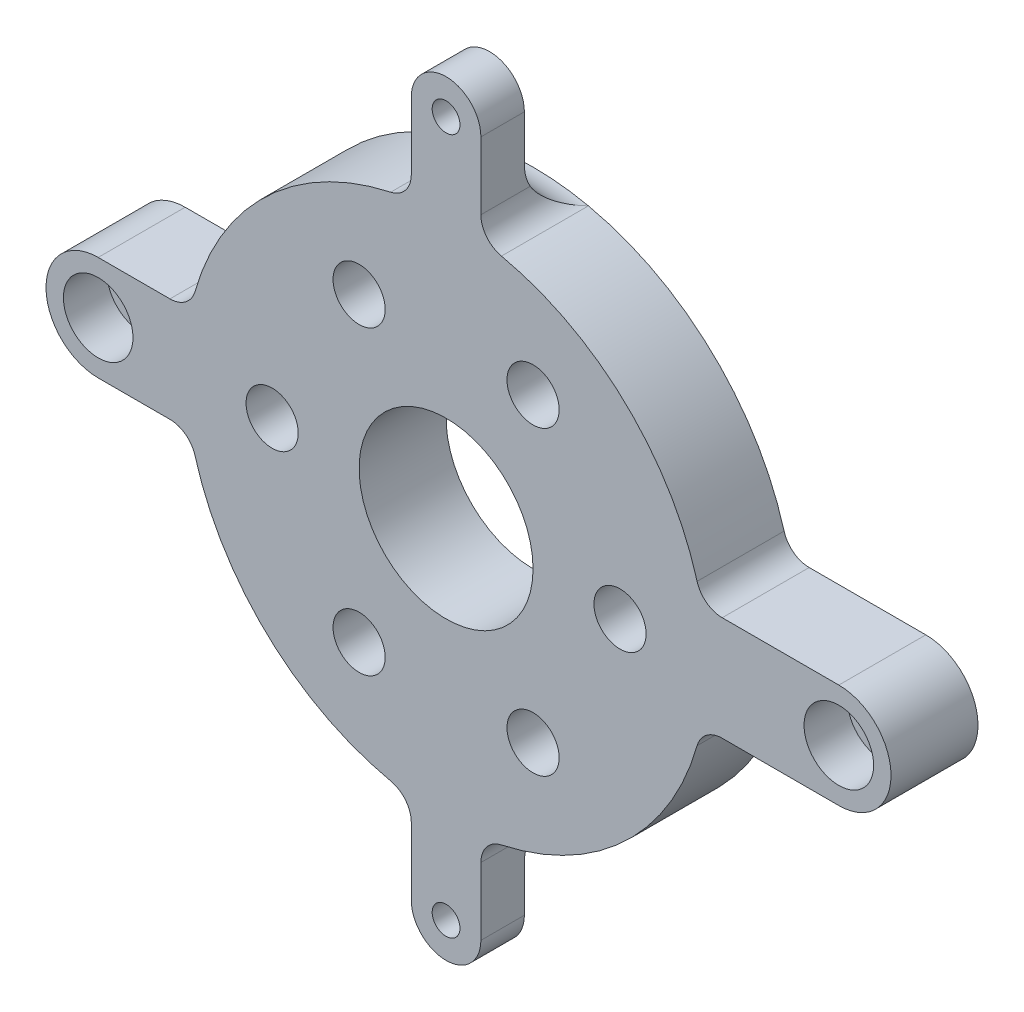
SolidWorks part; units mm, degrees
ref_plane "Plano frontal" through (0, 0, 0) normal (0, 0, 1) x (1, 0, 0)
ref_plane "Plano superior" through (0, 0, 0) normal (0, 1, 0) x (1, 0, 0)
ref_plane "Plano direito" through (0, 0, 0) normal (1, 0, 0) x (0, 0, -1)
sketch "Esboço1" plane through (0, 0, 0) normal (0, 0, 1) x (1, 0, 0)
  line L0 (-200, 30) -> (-158.7451, 30)
  line L1 (-200, -30) -> (-158.7451, -30)
  line L2 (225.7859, 30) -> (158.7451, 30)
  line L3 (225.7859, -30) -> (158.7451, -30)
  line L4 (-20, 200) -> (-20, 148.6607)
  line L5 (20, 200) -> (20, 148.6607)
  line L6 (20, -200) -> (20, -148.6607)
  line L7 (-20, -200) -> (-20, -148.6607)
  arc A0 (-144.3137, -40.9091) -> (144.3137, -40.9091) centre (0, 0) ccw
  arc A1 (-200, 30) -> (-200, -30) centre (-200, 0) ccw
  arc A2 (225.7859, -30) -> (225.7859, 30) centre (225.7859, 0) ccw
  arc A4 (144.3137, 40.9091) -> (20, 148.6607) centre (0, 0) ccw
  arc A5 (-158.7451, 30) -> (-144.3137, 40.9091) centre (-158.7451, 45) ccw
  arc A6 (158.7451, -30) -> (144.3137, -40.9091) centre (158.7451, -45) ccw
  arc A7 (158.7451, 30) -> (144.3137, 40.9091) centre (158.7451, 45) cw
  arc A8 (-158.7451, -30) -> (-144.3137, -40.9091) centre (-158.7451, -45) cw
  circle A9 centre (-200, 0) radius 10
  circle A10 centre (225.7859, 0) radius 10
  circle A11 centre (0, 0) radius 50
  circle A13 centre (100, 0) radius 15
  circle A14 centre (50, -86.6025) radius 15
  circle A15 centre (-50, -86.6025) radius 15
  circle A16 centre (-100, 0) radius 15
  circle A17 centre (-50, 86.6025) radius 15
  circle A18 centre (50, 86.6025) radius 15
  circle A19 centre (225.7859, 0) radius 20
  circle A20 centre (-200, 0) radius 20
  circle A21 centre (0, 200) radius 8
  arc A22 (20, 200) -> (-20, 200) centre (0, 200) ccw
  arc A23 (-20, 148.6607) -> (-144.3137, 40.9091) centre (0, 0) ccw
  arc A24 (-31.8182, 146.5865) -> (-20, 161.2452) centre (-35, 161.2452) ccw
  arc A25 (20, 161.2452) -> (31.8182, 146.5865) centre (35, 161.2452) ccw
  arc A26 (-20, 148.6607) -> (20, 148.6607) centre (0, 0) cw
  arc A27 (31.8182, -146.5865) -> (20, -161.2452) centre (35, -161.2452) ccw
  arc A28 (-20, -200) -> (20, -200) centre (0, -200) ccw
  circle A29 centre (0, -200) radius 8
  arc A30 (-20, -161.2452) -> (-31.8182, -146.5865) centre (-35, -161.2452) ccw
  point P6 (-146.9694, 30)
  point P19 (146.9694, 30)
  point P22 (-146.9694, -30)
  point P41 (0, 0)
  point P50 (35, -155.907)
  point P51 (0, 0)
  point P67 (0, 0)
  point P68 (20, 146.5865)
  dimension "D1" = 300
  dimension "D2" = 200
  dimension "D4" = 60
  dimension "D5" = 15
  dimension "D6" = 15
  dimension "D7" = 20
  dimension "D8" = 20
  dimension "D9" = 100
  dimension "D10" = 30
  dimension "D14" = 40
  dimension "D15" = 40
  dimension "D16" = 16
  dimension "D18" = 30
  dimension "D19" = 2
  dimension "D3" = 225.7859
  dimension "D11" = 6
  dimension "D12" = 100
  dimension "D13" = 100
  dimension "D17" = 200
extrude "Ressalto-extrusão6" add sketch "Esboço1" along normal blind 25 contours L4 A26 L5 A22 A21 | A25 L5 A4 | A24 A23 L4 | A26 A23 A5 L0 A1 L1 A8 A0 A6 L3 A2 L2 A7 A4 A11 A13 A14 A15 A16 A17 A18 A19 A20 | A30 L7 A0 | A27 A0 L6 | L7 A28 L6 A0 A29 region at (-179.3725, 24.2905, 0) region at (-22.5896, 151.0384, 0) region at (0, 181.3646, 0) region at (-22.5896, -151.0384, 0) region at (22.5896, 151.0384, 0) region at (0, -181.3646, 0) region at (22.5896, -151.0384, 0)
extrude "Ressalto-extrusão7" add sketch "Esboço1<10>" against normal blind 25 contours A26 A23 A5 L0 A1 L1 A8 A0 A6 L3 A2 L2 A7 A4 A11 A13 A14 A15 A16 A17 A18 A19 A20 | A19 A10 | A20 A9 region at (-179.3725, 24.2905, 0) region at (206.3516, 0, 0) region at (-219.4343, 0, 0)
sketch "Esboço1<10>" plane through (0, 0, 0) normal (0, 0, 1) x (1, 0, 0) same geometry as "Esboço1"
fillet "Filete3" radius 25 1 edges at (0, 150, 0)
fillet "Filete4" radius 25 1 edges at (0, -150, 0)
